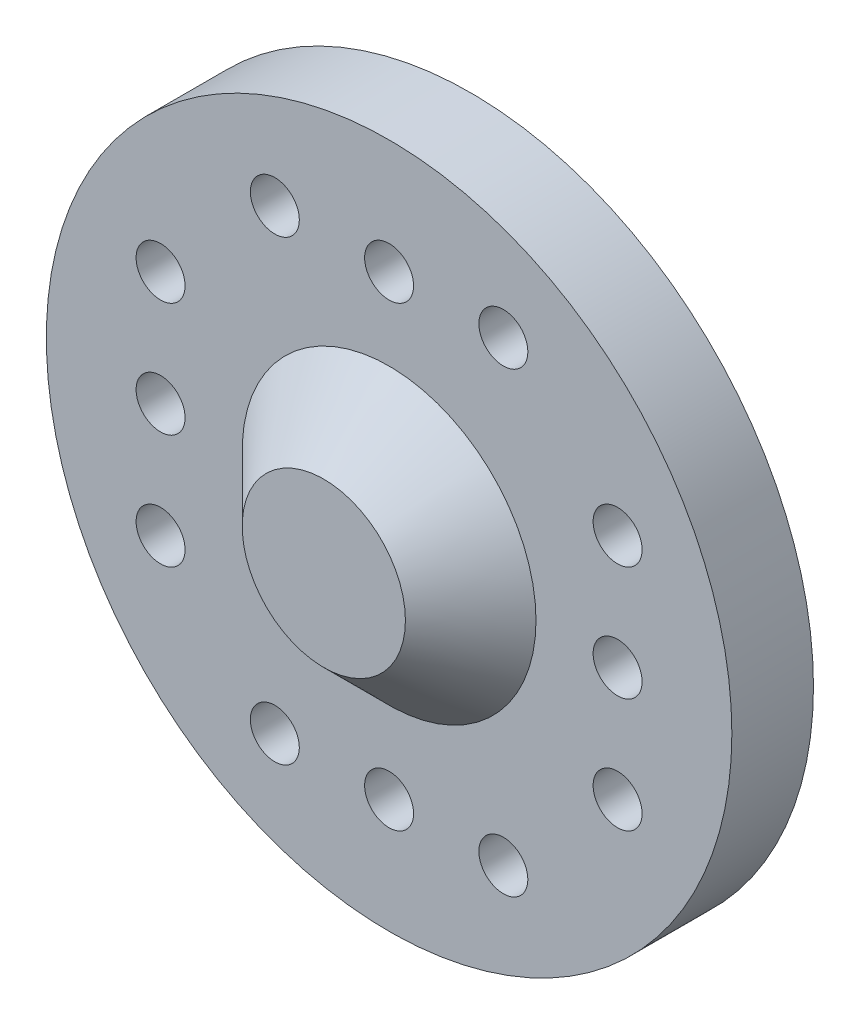
SolidWorks part; units mm, degrees
ref_plane "Front Plane" through (0, 0, 0) normal (0, 0, 1) x (1, 0, 0)
ref_plane "Top Plane" through (0, 0, 0) normal (0, 1, 0) x (1, 0, 0)
ref_plane "Right Plane" through (0, 0, 0) normal (1, 0, 0) x (0, 0, -1)
sketch "Sketch1" plane through (0, 0, 0) normal (0, 0, 1) x (1, 0, 0)
  circle A0 centre (0, 0) radius 10.5
  dimension "D1" = 21
extrude "Boss-Extrude1" add sketch "Sketch1" along normal blind 2.5
sketch "Sketch3" plane through (0, 0, 2.5) normal (0, 0, 1) x (1, 0, 0)
  circle A0 centre (0, 0) radius 4.5
  dimension "D1" = 9
extrude "Boss-Extrude2" add sketch "Sketch3" along normal blind 2
chamfer "Chamfer1" distance 2 angle 45 1 edges at (4.5, 0, 4.5)
sketch "Sketch4" plane through (0, 0, 2.5) normal (0, 0, 1) x (1, 0, 0)
  line L0 (0, 0) -> (0, 10.5) construction
  line L1 (0, 0) -> (0, -10.5) construction
  line L2 (0, 0) -> (10.5, 0) construction
  line L3 (0, 0) -> (-10.5, 0) construction
  line L4 (0, 7) -> (10.1254, 7) construction
  line L5 (10.1254, 7) -> (-9.907, 7) construction
  line L6 (7, 0) -> (7, -9.3281) construction
  line L7 (7, -9.3281) -> (7, 11.6163) construction
  line L8 (-7, 0) -> (-7, -10.5) construction
  line L9 (9.8876, -7) -> (-9.907, -7) construction
  line L10 (-7, -10.5) -> (-7, 9.0982) construction
  circle A0 centre (0, 0) radius 10.5 construction
  circle A1 centre (0, 7) radius 0.75
  circle A2 centre (7, 0) radius 0.75
  circle A3 centre (0, -7) radius 0.75
  circle A4 centre (-7, 0) radius 0.75
  circle A5 centre (3.5, 7) radius 0.75
  circle A6 centre (-3.5, 7) radius 0.75
  circle A7 centre (7, -3.5) radius 0.75
  circle A8 centre (7, 3.5) radius 0.75
  circle A9 centre (3.5, -7) radius 0.75
  circle A10 centre (-3.5, -7) radius 0.75
  circle A11 centre (-7, -3.5) radius 0.75
  circle A12 centre (-7, 3.5) radius 0.75
  point P43 (27.8455, 0.6743)
  dimension "D2" = 1.5
  dimension "D7" = 1.5
  dimension "D9" = 1.5
  dimension "D10" = 1.5
  dimension "D11" = 1.5
  dimension "D12" = 1.5
  dimension "D13" = 1.5
  dimension "D14" = 1.5
  dimension "D15" = 1.5
  dimension "D16" = 1.5
  dimension "D17" = 1.5
  dimension "D18" = 1.5
  dimension "D1" = 7
  dimension "D3" = 7
  dimension "D4" = 7
  dimension "D5" = 7
  dimension "D6" = 3.5
  dimension "D8" = 3.5
  dimension "D19" = 3.5
  dimension "D20" = 3.5
  dimension "D21" = 3.5
  dimension "D22" = 3.5
  dimension "D23" = 3.5
  dimension "D24" = 3.5
extrude "Cut-Extrude1" cut sketch "Sketch4" against normal through all
